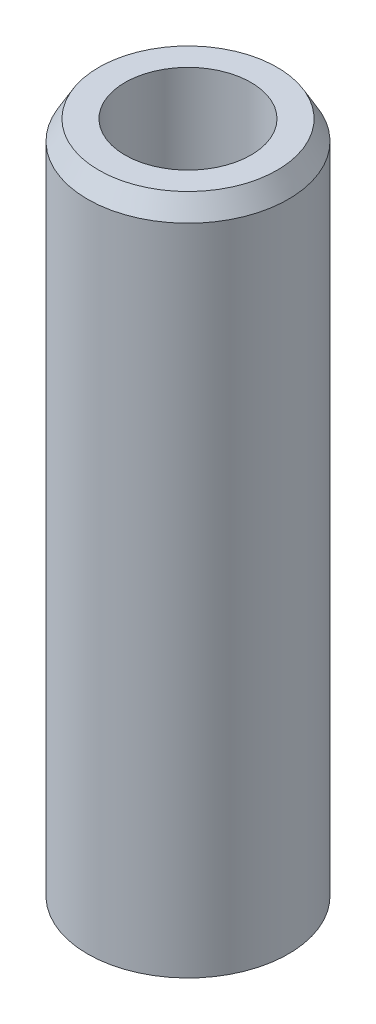
SolidWorks part; units mm, degrees
ref_plane "Front Plane" through (0, 0, 0) normal (0, 0, 1) x (1, 0, 0)
ref_plane "Top Plane" through (0, 0, 0) normal (0, 1, 0) x (1, 0, 0)
ref_plane "Right Plane" through (0, 0, 0) normal (1, 0, 0) x (0, 0, -1)
sketch "Sketch1" plane through (0, 0, 0) normal (0, 1, 0) x (1, 0, 0)
  circle A0 centre (0, 0) radius 7.5
  dimension "SHAFT_OD" = 15
extrude "Boss-Extrude1" add sketch "Sketch1" along normal blind 51.1065
sketch "Sketch2" plane through (0, 0, 0) normal (0, 1, 0) x (1, 0, 0)
  circle A0 centre (0, 0) radius 4.702
  dimension "BORE_D" = 9.4041
extrude "Cut-Extrude1" cut sketch "Sketch2" along normal through all
chamfer "Chamfer1" distance 1.4568 angle 30 2 edges at (0, 51.1065, 7.5) (0, 0, 7.5) first distance on face at (0, 51.1065, 7.5) first distance on face at (0, 0, 4.702)
